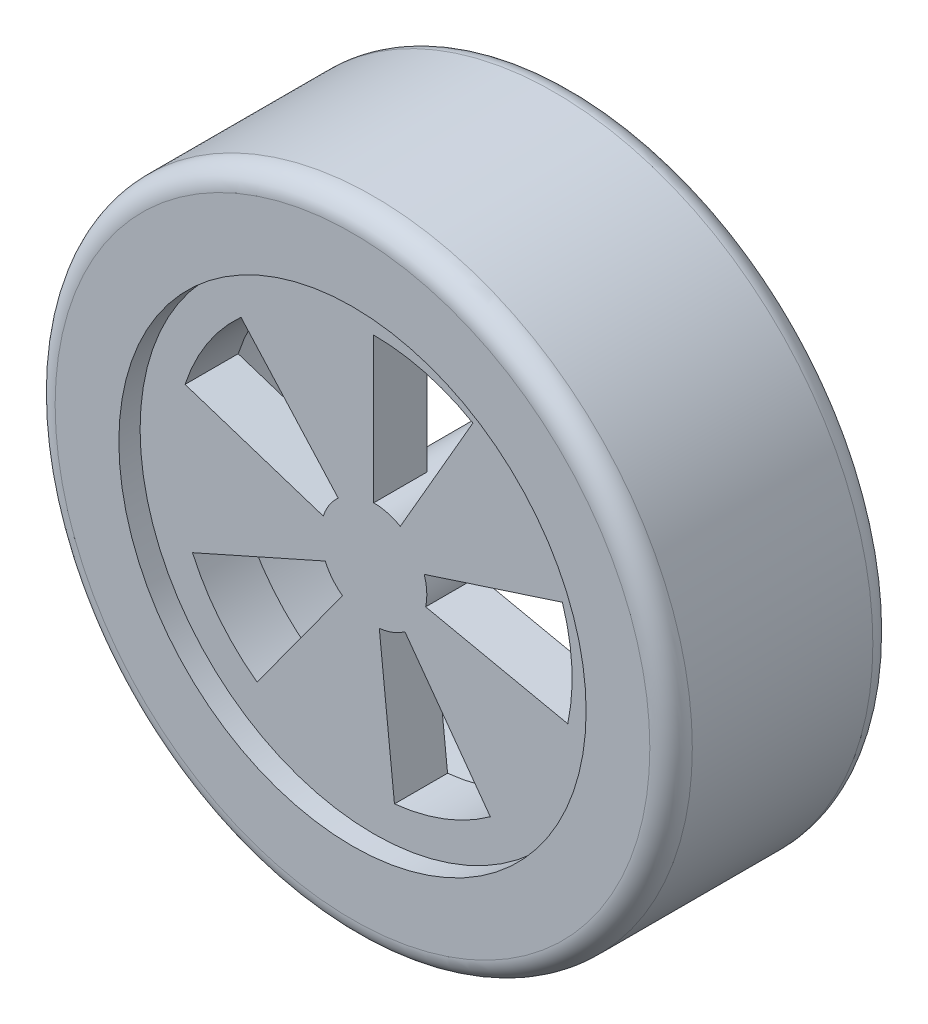
SolidWorks part; units mm, degrees
ref_plane "Front Plane" through (0, 0, 0) normal (0, 0, 1) x (1, 0, 0)
ref_plane "Top Plane" through (0, 0, 0) normal (0, 1, 0) x (1, 0, 0)
ref_plane "Right Plane" through (0, 0, 0) normal (1, 0, 0) x (0, 0, -1)
sketch "Sketch1" plane through (0, 0, 0) normal (0, 0, 1) x (1, 0, 0)
  circle A0 centre (0, 0) radius 15
extrude "Boss-Extrude1" add sketch "Sketch1" along normal blind 10.5 contours A0
sketch "Sketch2" plane through (0, 0, 10.5) normal (0, 0, 1) x (1, 0, 0)
  circle A0 centre (0, 0) radius 11
extrude "Cut-Extrude1" cut sketch "Sketch2" against normal blind 1
sketch "Sketch3" plane through (0, 0, 0) normal (0, 0, -1) x (-1, 0, 0)
  circle A0 centre (0, 0) radius 12
  circle A1 centre (0, 0) radius 2.5
  circle A2 centre (0, 0) radius 1
extrude "Cut-Extrude2" cut sketch "Sketch3" against normal blind 7 contours A0 A1 | A2 region at (11.6606, 0, 0) region at (0, 0, 0)
extrude "Boss-Extrude2" add sketch "Sketch3<4>" along normal blind 2.5 contours A1 A2 region at (2.4293, 0, 0)
sketch "Sketch3<4>" plane through (0, 0, 0) normal (0, 0, -1) x (-1, 0, 0) same geometry as "Sketch3"
fillet "Fillet1" radius 1 2 edges at (15, 0, 0) (15, 0, 10.5)
sketch "Sketch4" plane through (0, 0, 9.5) normal (0, 0, 1) x (1, 0, 0)
  line L0 (0, 2.5) -> (0, 9.3396)
  line L1 (1.25, 2.1651) -> (4.6698, 8.0883)
  line L2 (2.3776, 0.7725) -> (8.8825, 2.8861)
  line L3 (2.4454, -0.5198) -> (9.1355, -1.9418)
  line L4 (1.4695, -2.0225) -> (5.4897, -7.5559)
  line L5 (0.2613, -2.4863) -> (0.9763, -9.2884)
  line L6 (-1.4695, -2.0225) -> (-5.4897, -7.5559)
  line L7 (-2.2839, -1.0168) -> (-8.5322, -3.7988)
  line L8 (-2.3776, 0.7725) -> (-8.8825, 2.8861)
  line L9 (-1.6728, 1.8579) -> (-6.2494, 6.9407)
  arc A0 (4.6698, 8.0883) -> (0, 9.3396) centre (0, 0) ccw
  arc A2 (1.25, 2.1651) -> (0, 2.5) centre (0, 0) ccw
  arc A3 (9.1355, -1.9418) -> (8.8825, 2.8861) centre (0, 0) ccw
  arc A4 (2.4454, -0.5198) -> (2.3776, 0.7725) centre (0, 0) ccw
  arc A5 (0.9763, -9.2884) -> (5.4897, -7.5559) centre (0, 0) ccw
  arc A6 (0.2613, -2.4863) -> (1.4695, -2.0225) centre (0, 0) ccw
  arc A7 (-8.5322, -3.7988) -> (-5.4897, -7.5559) centre (0, 0) ccw
  arc A8 (-2.2839, -1.0168) -> (-1.4695, -2.0225) centre (0, 0) ccw
  arc A9 (-6.2494, 6.9407) -> (-8.8825, 2.8861) centre (0, 0) ccw
  arc A10 (-1.6728, 1.8579) -> (-2.3776, 0.7725) centre (0, 0) ccw
  point P3 (0, 0)
  point P9 (0, 0)
  point P14 (0, 0)
  point P19 (0, 0)
  point P24 (0, 0)
  point P29 (0, 0)
  dimension "D1" = 30
  dimension "D2" = 5
extrude "Cut-Extrude3" cut sketch "Sketch4" against normal through all
